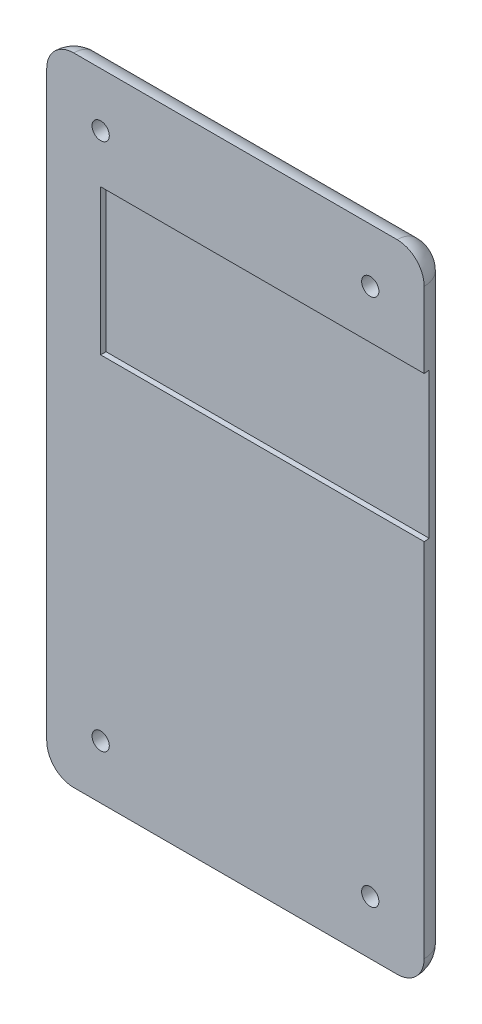
SolidWorks part; units mm, degrees
ref_plane "正面" through (0, 0, 0) normal (0, 0, 1) x (1, 0, 0)
ref_plane "平面" through (0, 0, 0) normal (0, 1, 0) x (1, 0, 0)
ref_plane "右側面" through (0, 0, 0) normal (1, 0, 0) x (0, 0, -1)
sketch "ｽｹｯﾁ1" plane through (0, 0, 0) normal (0, 0, 1) x (1, 0, 0)
  line L1 (-35, -59) -> (35, -59)
  line L2 (-35, -59) -> (-35, 59)
  line L3 (-35, 59) -> (35, 59)
  line L4 (35, -59) -> (35, 59)
  line L5 (-35, -59) -> (35, 59) construction
  line L6 (-35, 59) -> (35, -59) construction
  point P0 (0, 0)
  dimension "D1" = 118
  dimension "D2" = 70
extrude "ﾎﾞｽ - 押し出し1" add sketch "ｽｹｯﾁ1" along normal blind 40
sketch "ｽｹｯﾁ2" plane through (0, 0, 40) normal (0, 0, 1) x (1, 0, 0)
  line L1 (-32, -56) -> (32, -56)
  line L2 (-32, -56) -> (-32, 56)
  line L3 (-32, 56) -> (32, 56)
  line L4 (32, -56) -> (32, 56)
  line L5 (-32, -56) -> (32, 56) construction
  line L6 (-32, 56) -> (32, -56) construction
  point P0 (0, 0)
  dimension "D1" = 112
  dimension "D2" = 64
extrude "ｶｯﾄ - 押し出し1" cut sketch "ｽｹｯﾁ2" against normal blind 35
sketch "ｽｹｯﾁ3" plane through (0, 0, 5) normal (0, 0, 1) x (1, 0, 0)
  line L1 (-25, -49) -> (25, -49) construction
  line L2 (-25, -49) -> (-25, 49) construction
  line L3 (-25, 49) -> (25, 49) construction
  line L4 (25, -49) -> (25, 49) construction
  line L5 (-25, -49) -> (25, 49) construction
  line L6 (-25, 49) -> (25, -49) construction
  circle A0 centre (-25, 49) radius 1.6
  circle A1 centre (25, 49) radius 1.6
  circle A2 centre (-25, -49) radius 1.6
  circle A3 centre (25, -49) radius 1.6
  point P0 (0, 0)
  dimension "D1" = 50
  dimension "D2" = 98
  dimension "D3" = 3.2
  dimension "D4" = 3.2
  dimension "D5" = 3.2
  dimension "D6" = 3.2
extrude "ｶｯﾄ - 押し出し2" cut sketch "ｽｹｯﾁ3" against normal through all
fillet "ﾌｨﾚｯﾄ1" radius 5 4 edges at (0, -59, 0) (0, 59, 0) (-35, 0, 0) (35, 0, 0)
fillet "ﾌｨﾚｯﾄ2" radius 5 8 edges at (-33.5355, 57.5355, 1.4645) (-33.5355, -57.5355, 1.4645) (33.5355, 57.5355, 1.4645) (33.5355, -57.5355, 1.4645) (-35, 59, 22.5) (-35, -59, 22.5) (35, 59, 22.5) (35, -59, 22.5)
sketch "ｽｹｯﾁ4" plane through (0, 0, 40) normal (0, 0, 1) x (1, 0, 0)
  line L1 (40, 60) -> (-40, 60)
  line L2 (40, 60) -> (40, -60)
  line L3 (40, -60) -> (-40, -60)
  line L4 (-40, 60) -> (-40, -60)
  line L5 (40, 60) -> (-40, -60) construction
  line L6 (40, -60) -> (-40, 60) construction
  point P0 (0, 0)
  dimension "D1" = 120
  dimension "D2" = 80
extrude "ｶｯﾄ - 押し出し3" cut sketch "ｽｹｯﾁ4" against normal blind 35
sketch "ｽｹｯﾁ5" plane through (0, 0, 5) normal (0, 0, 1) x (1, 0, 0)
  line L0 (35, -54) -> (35, 54) construction
  line L1 (35, 13) -> (-25, 13)
  line L2 (35, 13) -> (35, 40)
  line L3 (35, 40) -> (-25, 40)
  line L4 (-25, 13) -> (-25, 40)
  line L5 (30, 59) -> (-30, 59) construction
  dimension "D1" = 27
  dimension "D2" = 60
  dimension "D3" = 19
extrude "ｶｯﾄ - 押し出し4" cut sketch "ｽｹｯﾁ5" against normal blind 1
